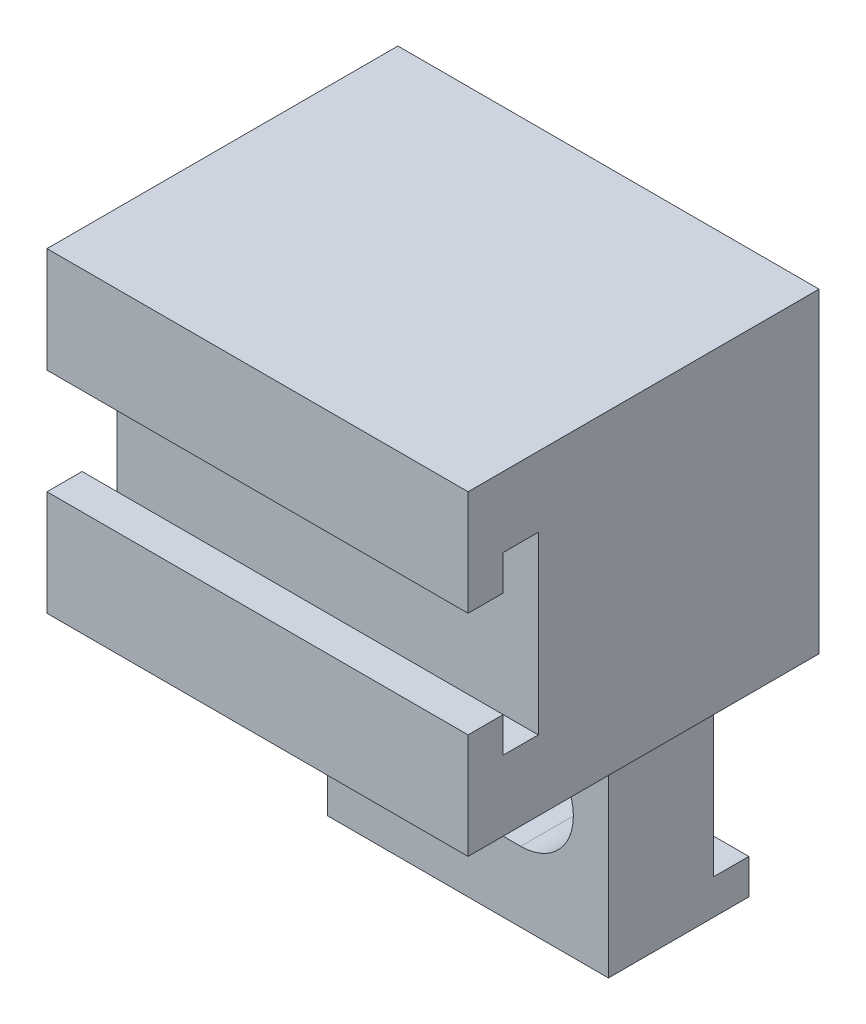
SolidWorks part; units mm, degrees
ref_plane "Front Plane" through (0, 0, 0) normal (1, 0, 0) x (0, 1, 0)
ref_plane "Top Plane" through (0, 0, 0) normal (0, 0, 1) x (0, 1, 0)
ref_plane "Right Plane" through (0, 0, 0) normal (0, 1, 0) x (-1, 0, 0)
sketch "Sketch1" plane through (0, 0, 0) normal (1, 0, 0) x (0, 1, 0)
  line L0 (0, 0) -> (10, 0)
  line L1 (10, 0) -> (10, 10)
  line L2 (10, 10) -> (60, 10)
  line L3 (60, 10) -> (60, 0)
  line L4 (60, 0) -> (70, 0)
  line L5 (70, 0) -> (70, 40)
  line L6 (70, 40) -> (0, 40)
  line L7 (0, 40) -> (0, 0)
  line L8 (70, 0) -> (160, 0)
  line L9 (160, 0) -> (160, 100)
  line L10 (160, 100) -> (130, 100)
  line L11 (130, 100) -> (130, 90)
  line L12 (130, 90) -> (140, 90)
  line L13 (140, 90) -> (140, 80)
  line L14 (140, 80) -> (90, 80)
  line L15 (90, 80) -> (90, 90)
  line L16 (90, 90) -> (100, 90)
  line L17 (100, 90) -> (100, 100)
  line L18 (100, 100) -> (70, 100)
  line L19 (70, 100) -> (70, 0)
  line L20 (115, 0) -> (115, 29.9535) construction
  point P19 (100, 95)
  dimension "D1" = 40
  dimension "D2" = 10
  dimension "D3" = 50
  dimension "D4" = 10
  dimension "D5" = 10
  dimension "D6" = 100
  dimension "D7" = 20
  dimension "D8" = 20
  dimension "D9" = 30
  dimension "D10" = 50
  dimension "D11" = 10
  dimension "D12" = 10
extrude "Boss-Extrude1" add sketch "Sketch1" along normal mid plane 120 contours L18 L19 L5 L8 L9 L10 L11 L12 L13 L14 L15 L16 L17 region at (0, 115, 46.2195)
extrude "Boss-Extrude2" add sketch "Sketch1<3>" along normal mid plane 80 contours L6 L7 L0 L1 L2 L3 L4 L5 region at (0, 35, 23.2609)
sketch "Sketch1<3>" plane through (0, 0, 0) normal (1, 0, 0) x (0, 1, 0) same geometry as "Sketch1"
sketch "Sketch2" plane through (0, 0, 40) normal (0, 0, 1) x (1, 0, 0)
  line L0 (-15, 35) -> (15, 35) construction
  line L1 (-15, 50) -> (15, 50)
  line L2 (-15, 20) -> (15, 20)
  line L3 (-40, 70) -> (-40, 0) construction
  arc A0 (-15, 50) -> (-15, 20) centre (-15, 35) ccw
  arc A1 (15, 20) -> (15, 50) centre (15, 35) ccw
  point P2 (0, 35)
  point P7 (0, 0)
  point P11 (-40, 35)
  dimension "D2" = 15
  dimension "D1" = 30
extrude "Cut-Extrude1" cut sketch "Sketch2" against normal through all both and the other way through all
